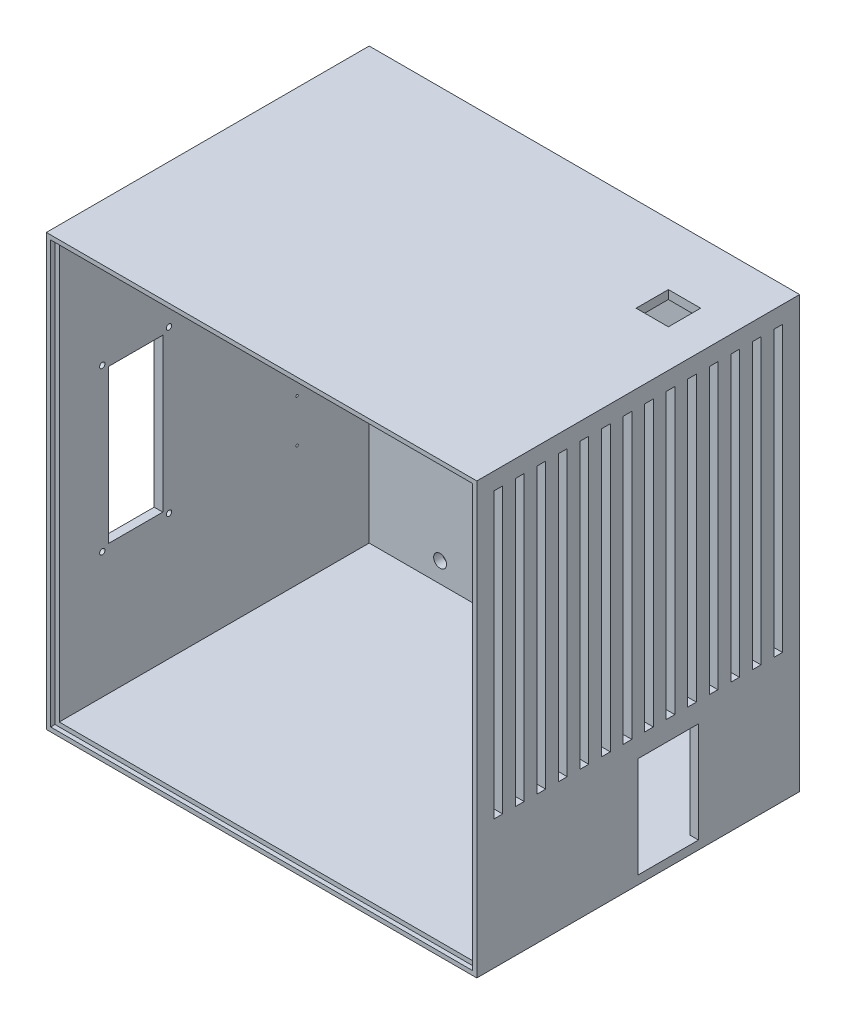
SolidWorks part; units mm, degrees
ref_plane "Front Plane" through (0, 0, 0) normal (0, 0, 1) x (1, 0, 0)
ref_plane "Top Plane" through (0, 0, 0) normal (0, 1, 0) x (1, 0, 0)
ref_plane "Right Plane" through (0, 0, 0) normal (1, 0, 0) x (0, 0, -1)
sketch "Sketch4" plane through (0, 0, 0) normal (0, 0, 1) x (1, 0, 0)
  line L1 (0, 0) -> (200, 0)
  line L2 (0, 0) -> (0, 200)
  line L3 (0, 200) -> (200, 200)
  line L4 (200, 0) -> (200, 200)
  dimension "D1" = 200
  dimension "D2" = 200
extrude "Boss-Extrude1" add sketch "Sketch4" along normal blind 150 contours L2 L1 L4 L3
sketch "Sketch5" plane through (0, 0, 150) normal (0, 0, 1) x (1, 0, 0)
  line L0 (100, 0) -> (100, 2) construction
  line L1 (0, 0) -> (200, 0) construction
  line L2 (0, 100) -> (2, 100) construction
  line L6 (200, 100) -> (198, 100) construction
  line L7 (200, 0) -> (200, 200) construction
  line L8 (100, 200) -> (100, 198) construction
  line L9 (0, 200) -> (200, 200) construction
  line L10 (100, 198) -> (198, 198) construction
  line L11 (198, 198) -> (198, 100) construction
  line L12 (0, 0) -> (0, 200) construction
  line L13 (2, 100) -> (198, 100)
  point P11 (0, 100)
  point P14 (0, 100)
  dimension "D1" = 2
  dimension "D2" = 2
  dimension "D3" = 2
sketch "Sketch6" plane through (0, 0, 150) normal (0, 0, 1) x (1, 0, 0)
  line L0 (2, 100) -> (198, 100) construction
  line L1 (2, 2) -> (198, 2)
  line L2 (2, 2) -> (2, 198)
  line L3 (2, 198) -> (198, 198)
  line L4 (198, 2) -> (198, 198)
  line L5 (2, 2) -> (198, 198) construction
  line L6 (2, 198) -> (198, 2) construction
  point P0 (100, 100)
extrude "Cut-Extrude1" cut sketch "Sketch6" against normal blind 2 contours L2 L1 L4 L3
sketch "Sketch7" plane through (0, 0, 148) normal (0, 0, 1) x (1, 0, 0)
  line L0 (100, 198) -> (100, 196) construction
  line L1 (2, 100) -> (4, 100) construction
  line L2 (2, 100) -> (198, 100) construction
  line L3 (198, 100) -> (196, 100) construction
  line L4 (100, 2) -> (100, 4) construction
  line L6 (4, 4) -> (196, 4)
  line L7 (4, 4) -> (4, 196)
  line L8 (4, 196) -> (196, 196)
  line L9 (196, 4) -> (196, 196)
  line L10 (4, 4) -> (196, 196) construction
  line L11 (4, 196) -> (196, 4) construction
  point P14 (100, 100)
  dimension "D1" = 2
  dimension "D2" = 2
  dimension "D3" = 2
extrude "Cut-Extrude2" cut sketch "Sketch7" against normal blind 92
sketch "Sketch9" plane through (200, 0, 0) normal (1, 0, 0) x (0, 0, -1)
  line L0 (-150, 100) -> (0, 100) construction
  line L1 (-150, 0) -> (-150, 200) construction
  line L2 (0, 0) -> (0, 200) construction
  line L3 (-75, 200) -> (-75, 0) construction
  line L4 (-150, 0) -> (0, 0) construction
  line L5 (0, 0) -> (0, 4) construction
  line L6 (0, 0) -> (-4, 0) construction
  line L7 (-4, 0) -> (-4, 4) construction
  line L8 (-4, 4) -> (0, 4) construction
  line L9 (-4, 4) -> (-150, 4) construction
  line L10 (-75, 0) -> (-75, 4) construction
  line L11 (-150, 200) -> (0, 200) construction
  line L12 (-75, 4) -> (-47, 4)
  line L13 (-75, 4) -> (-75, 50.8)
  line L14 (-75, 50.8) -> (-47, 50.8)
  line L15 (-47, 4) -> (-47, 50.8)
  dimension "D1" = 4
  dimension "D2" = 4
  dimension "D3" = 28
  dimension "D4" = 46.8
sketch "Sketch11" plane through (0, 0, 0) normal (-1, 0, 0) x (0, 0, 1)
  line L0 (75, 0) -> (75, 200) construction
  line L2 (150, 0) -> (0, 0) construction
  line L3 (150, 200) -> (0, 200) construction
  line L5 (150, 0) -> (150, 200) construction
  line L6 (75, 0) -> (75, 4) construction
  line L7 (150, 100) -> (146, 100) construction
  line L10 (75, 4) -> (150, 4) construction
  line L11 (146, 100) -> (146, 4) construction
  line L12 (75, 100) -> (150, 100) construction
  line L13 (99.9, 64.4) -> (125.1, 64.4)
  line L14 (99.9, 64.4) -> (99.9, 135.6)
  line L15 (99.9, 135.6) -> (125.1, 135.6)
  line L16 (125.1, 64.4) -> (125.1, 135.6)
  line L17 (99.9, 64.4) -> (125.1, 135.6) construction
  line L18 (99.9, 135.6) -> (125.1, 64.4) construction
  line L19 (94.5, 60) -> (130.5, 60)
  line L20 (94.5, 60) -> (94.5, 140)
  line L21 (94.5, 140) -> (130.5, 140)
  line L22 (130.5, 60) -> (130.5, 140)
  line L23 (94.5, 60) -> (130.5, 140) construction
  line L24 (94.5, 140) -> (130.5, 60) construction
  line L25 (97, 62.5) -> (128, 62.5)
  line L26 (97, 62.5) -> (97, 137.5)
  line L27 (97, 137.5) -> (128, 137.5)
  line L28 (128, 62.5) -> (128, 137.5)
  line L29 (97, 62.5) -> (128, 137.5) construction
  line L30 (97, 137.5) -> (128, 62.5) construction
  circle A0 centre (128, 137.5) radius 1.25
  circle A1 centre (97, 137.5) radius 1.25
  circle A2 centre (97, 62.5) radius 1.25
  circle A3 centre (128, 62.5) radius 1.25
  point P8 (112.5, 100)
  point P19 (112.5, 100)
  point P24 (112.5, 100)
  dimension "D1" = 4
  dimension "D2" = 4
  dimension "D9" = 2.5
  dimension "D10" = 2.5
  dimension "D11" = 2.5
  dimension "D12" = 2.5
  dimension "D3" = 25.2
  dimension "D4" = 71.2
  dimension "D5" = 36
  dimension "D6" = 80
  dimension "D7" = 75
  dimension "D8" = 31
sketch "Sketch12" plane through (0, 0, 0) normal (-1, 0, 0) x (0, 0, 1)
  line L0 (75, 200) -> (75, 0) construction
  line L1 (150, 200) -> (0, 200) construction
  line L2 (150, 0) -> (0, 0) construction
  line L3 (75, 100) -> (0, 100) construction
  line L4 (150, 0) -> (150, 200) construction
  line L5 (0, 0) -> (0, 200) construction
  line L6 (0, 200) -> (4, 200) construction
  line L7 (0, 200) -> (0, 196) construction
  line L8 (4, 200) -> (4, 0) construction
  line L9 (0, 196) -> (150, 196) construction
  line L10 (37.5, 100) -> (37.5, 196) construction
  line L11 (37.5, 100) -> (37.5, 0) construction
  circle A0 centre (37.5, 100) radius 0.55
  circle A1 centre (37.5, 80) radius 0.55
  circle A2 centre (37.5, 60) radius 0.55
  circle A3 centre (37.5, 148) radius 1
  dimension "D1" = 4
  dimension "D2" = 4
  dimension "D3" = 1.1
  dimension "D5" = 2
sketch "Sketch13" plane through (200, 0, 0) normal (1, 0, 0) x (0, 0, -1)
  line L0 (-4, 4) -> (-4, 200) construction
  line L1 (-150, 200) -> (0, 200) construction
  line L2 (-75, 200) -> (-75, 196) construction
  line L3 (-75, 200) -> (-75, 0) construction
  line L4 (-150, 100) -> (-146, 100) construction
  line L5 (-150, 100) -> (0, 100) construction
  line L6 (-4, 196) -> (-146, 196) construction
  line L7 (-146, 196) -> (-146, 4) construction
  line L8 (-4, 4) -> (-150, 4) construction
  line L9 (-4, 196) -> (-4, 192) construction
  line L10 (-4, 196) -> (-8, 196) construction
  line L11 (-8, 196) -> (-8, 192) construction
  line L12 (-8, 192) -> (-4, 192) construction
  line L13 (-75, 100) -> (-75, 60) construction
  line L14 (-75, 60) -> (-4, 60) construction
  line L15 (-146, 196) -> (-142, 196) construction
  line L16 (-8, 192) -> (-12, 192)
  line L17 (-8, 192) -> (-8, 60)
  line L18 (-8, 60) -> (-12, 60)
  line L19 (-12, 192) -> (-12, 60)
  line L20 (-146, 196) -> (-146, 192) construction
  line L21 (-142, 196) -> (-142, 192) construction
  line L22 (-142, 192) -> (-146, 192) construction
  line L23 (-18, 192) -> (-18, 60)
  line L24 (-18, 192) -> (-22, 192)
  line L25 (-22, 192) -> (-22, 60)
  line L26 (-18, 60) -> (-22, 60)
  line L27 (-28, 192) -> (-28, 60)
  line L28 (-28, 192) -> (-32, 192)
  line L29 (-32, 192) -> (-32, 60)
  line L30 (-28, 60) -> (-32, 60)
  line L31 (-38, 192) -> (-38, 60)
  line L32 (-38, 192) -> (-42, 192)
  line L33 (-42, 192) -> (-42, 60)
  line L34 (-38, 60) -> (-42, 60)
  line L35 (-48, 192) -> (-48, 60)
  line L36 (-48, 192) -> (-52, 192)
  line L37 (-52, 192) -> (-52, 60)
  line L38 (-48, 60) -> (-52, 60)
  line L39 (-58, 192) -> (-58, 60)
  line L40 (-58, 192) -> (-62, 192)
  line L41 (-62, 192) -> (-62, 60)
  line L42 (-58, 60) -> (-62, 60)
  line L43 (-68, 192) -> (-68, 60)
  line L44 (-68, 192) -> (-72, 192)
  line L45 (-72, 192) -> (-72, 60)
  line L46 (-68, 60) -> (-72, 60)
  line L47 (-78, 192) -> (-78, 60)
  line L48 (-78, 192) -> (-82, 192)
  line L49 (-82, 192) -> (-82, 60)
  line L50 (-78, 60) -> (-82, 60)
  line L51 (-88, 192) -> (-88, 60)
  line L52 (-88, 192) -> (-92, 192)
  line L53 (-92, 192) -> (-92, 60)
  line L54 (-88, 60) -> (-92, 60)
  line L55 (-98, 192) -> (-98, 60)
  line L56 (-98, 192) -> (-102, 192)
  line L57 (-102, 192) -> (-102, 60)
  line L58 (-98, 60) -> (-102, 60)
  line L59 (-108, 192) -> (-108, 60)
  line L60 (-108, 192) -> (-112, 192)
  line L61 (-112, 192) -> (-112, 60)
  line L62 (-108, 60) -> (-112, 60)
  line L63 (-118, 192) -> (-118, 60)
  line L64 (-118, 192) -> (-122, 192)
  line L65 (-122, 192) -> (-122, 60)
  line L66 (-118, 60) -> (-122, 60)
  line L67 (-128, 192) -> (-128, 60)
  line L68 (-128, 192) -> (-132, 192)
  line L69 (-132, 192) -> (-132, 60)
  line L70 (-128, 60) -> (-132, 60)
  line L71 (-138, 192) -> (-138, 60)
  line L72 (-138, 192) -> (-142, 192)
  line L73 (-142, 192) -> (-142, 60)
  line L74 (-138, 60) -> (-142, 60)
  dimension "D1" = 4
  dimension "D2" = 4
  dimension "D3" = 4
  dimension "D4" = 4
  dimension "D5" = 40
  dimension "D6" = 4
  dimension "D7" = 4
  dimension "D8" = 14
extrude "Inlet" cut sketch "Sketch9" against normal blind 4 contours L13 L12 L15 L14
extrude "Airflow" cut sketch "Sketch13" against normal blind 4
extrude "Cut-Extrude5" cut sketch "Sketch11" against normal blind 4 contours L14 L13 L16 L15
extrude "LCD/Mounting" cut sketch "Sketch11<4>" against normal blind 4 contours A2 | A0 | A1 | A3
sketch "Sketch11<4>" plane through (0, 0, 0) normal (-1, 0, 0) x (0, 0, 1) same geometry as "Sketch11"
extrude "Post/Knob Mounting" cut sketch "Sketch12" against normal blind 4
sketch "Sketch14" plane through (0, 0, 56) normal (0, 0, 1) x (1, 0, 0)
  line L0 (100, 4) -> (100, 109) construction
  line L1 (176, 9) -> (171.555, 9) construction
  line L2 (4, 4) -> (196, 4) construction
  line L3 (4, 4) -> (4, 9) construction
  line L4 (4, 196) -> (4, 4) construction
  line L5 (4, 9) -> (196, 9) construction
  line L6 (196, 4) -> (196, 50.8) construction
  line L7 (171.555, 9) -> (171.555, 13.318) construction
  line L8 (176, 108.06) -> (171.555, 108.06) construction
  line L9 (196, 4) -> (176, 4) construction
  line L10 (4, 4) -> (196, 4) construction
  line L11 (176, 4) -> (176, 9) construction
  line L12 (171.555, 108.06) -> (171.555, 104.25) construction
  line L13 (176, 9) -> (33.125, 9)
  line L14 (176, 9) -> (176, 108.06)
  line L15 (176, 108.06) -> (33.125, 108.06)
  line L16 (33.125, 9) -> (33.125, 108.06)
  line L17 (33.125, 9) -> (36.935, 9) construction
  line L18 (36.935, 9) -> (36.935, 13.318) construction
  line L19 (33.125, 108.06) -> (37.506, 108.06) construction
  line L20 (37.506, 108.06) -> (37.506, 103.996) construction
  line L22 (4, 196) -> (196, 196)
  line L23 (4, 196) -> (4, 4)
  line L24 (4, 4) -> (196, 4)
  line L25 (196, 196) -> (196, 4)
  circle A0 centre (36.935, 13.318) radius 3
  circle A1 centre (171.555, 13.318) radius 3
  circle A2 centre (171.555, 104.25) radius 3
  circle A3 centre (37.506, 103.996) radius 3
  dimension "D14" = 6
  dimension "D15" = 6
  dimension "D16" = 6
  dimension "D17" = 6
  dimension "D1" = 105
  dimension "D2" = 5
  dimension "D3" = 20
  dimension "D4" = 142.875
  dimension "D5" = 99.06
  dimension "D6" = 4.445
  dimension "D7" = 4.318
  dimension "D8" = 4.445
  dimension "D9" = 3.81
  dimension "D10" = 3.81
  dimension "D11" = 4.318
  dimension "D12" = 4.381
  dimension "D13" = 4.064
extrude "Cut-Extrude10" cut sketch "Sketch14" against normal blind 56 contours A3 | A2 | A0 | A1 region at (36.935, 13.318, 56) region at (171.555, 104.25, 56) region at (37.506, 103.996, 56)
sketch "Sketch17" plane through (0, 0, 56) normal (0, 0, 1) x (1, 0, 0)
  line L1 (4, 4) -> (196, 4)
  line L2 (4, 4) -> (4, 196)
  line L3 (4, 196) -> (196, 196)
  line L4 (196, 4) -> (196, 196)
extrude "Cut-Extrude11" cut sketch "Sketch17" against normal blind 52
sketch "Sketch18" plane through (0, 0, 4) normal (0, 0, 1) x (1, 0, 0)
  line L0 (100, 196) -> (100, 4) construction
  line L1 (196, 196) -> (4, 196) construction
  line L2 (4, 4) -> (196, 4) construction
  line L3 (4, 196) -> (4, 191) construction
  line L4 (4, 196) -> (4, 4) construction
  line L5 (4, 191) -> (196, 191) construction
  line L6 (196, 4) -> (196, 196) construction
  line L7 (4, 196) -> (52, 196) construction
  line L8 (196, 196) -> (4, 196) construction
  line L9 (196, 196) -> (148, 196) construction
  line L10 (52, 196) -> (76, 196) construction
  line L11 (76, 196) -> (76, 4) construction
  line L12 (76, 196) -> (76, 191) construction
  line L13 (142.04, 191) -> (126.8, 191) construction
  line L14 (76, 191) -> (142.04, 191)
  line L15 (76, 191) -> (76, 140.2)
  line L16 (76, 140.2) -> (142.04, 140.2)
  line L17 (142.04, 191) -> (142.04, 140.2)
  line L18 (126.8, 191) -> (126.8, 188.46) construction
  line L19 (126.8, 188.46) -> (126.8, 140.2) construction
  line L20 (126.8, 140.2) -> (126.8, 142.74) construction
  line L21 (76, 140.2) -> (76, 157.98) construction
  line L22 (76, 140.2) -> (76, 185.92)
  circle A0 centre (126.8, 188.46) radius 1.6
  circle A1 centre (126.8, 142.74) radius 1.6
  circle A2 centre (76, 157.98) radius 1.6
  circle A3 centre (76, 185.92) radius 1.6
  dimension "D12" = 3.2
  dimension "D13" = 3.2
  dimension "D14" = 3.2
  dimension "D15" = 3.2
  dimension "D1" = 5
  dimension "D2" = 48
  dimension "D3" = 48
  dimension "D4" = 24
  dimension "D5" = 66.04
  dimension "D6" = 50.8
  dimension "D7" = 15.24
  dimension "D8" = 2.54
  dimension "D9" = 2.54
  dimension "D10" = 17.78
  dimension "D11" = 45.72
extrude "Cut-Extrude12" cut sketch "Sketch18" against normal blind 4 contours A3 | A0 | A2 | A1
sketch "Sketch20" plane through (0, 200, 0) normal (0, 1, 0) x (1, 0, 0)
  line L0 (100, 0) -> (100, -150) construction
  line L1 (0, 0) -> (200, 0) construction
  line L2 (0, -150) -> (200, -150) construction
  line L3 (200, -72) -> (0, -72) construction
  line L4 (0, -150) -> (0, 0) construction
  line L5 (200, 0) -> (200, -36) construction
  line L6 (200, -150) -> (200, 0) construction
  line L7 (200, -36) -> (100, -36) construction
  line L8 (150, -36) -> (150, 0) construction
  line L9 (150, -18) -> (200, -18) construction
  line L10 (175, -18) -> (175, -36) construction
  line L12 (167.5, -28.5) -> (182.5, -28.5)
  line L13 (167.5, -28.5) -> (167.5, -43.5)
  line L14 (167.5, -43.5) -> (182.5, -43.5)
  line L15 (182.5, -28.5) -> (182.5, -43.5)
  line L16 (167.5, -28.5) -> (182.5, -43.5) construction
  line L17 (167.5, -43.5) -> (182.5, -28.5) construction
  dimension "D1" = 36
  dimension "D2" = 15
  dimension "D3" = 15
extrude "Cut-Extrude13" cut sketch "Sketch20" against normal blind 4 contours L13 L12 L15 L14
equation "\"L\"= 100mm"
equation "\"T\"= 1mm"
equation "\"D1@Sketch4\"=2*\"L\""
equation "\"D2@Sketch4\"=2*\"L\""
equation "\"D1@Boss-Extrude1\"=1.5*\"L\""
equation "\"D1@Sketch5\"=(1/50)*\"L\""
equation "\"D2@Sketch5\"=(1/50)*\"L\""
equation "\"D3@Sketch5\"=(1/50)*\"L\""
equation "\"D4@Sketch5\"=(1/50)*\"L\""
equation "\"D1@Cut-Extrude1\"=(1/50)*\"L\""
equation "\"D1@Sketch7\"=(1/50)*\"L\""
equation "\"D2@Sketch7\"=(1/50)*\"L\""
equation "\"D3@Sketch7\"=(1/50)*\"L\""
equation "\"D4@Sketch7\"=(1/50)*\"L\""
equation "\"D1@Sketch9\"=4*\"T\""
equation "\"D2@Sketch9\"=4*\"T\""
equation "\"D3@Sketch9\"=(7/25)*\"L\""
equation "\"D4@Sketch9\"=(46.8/100)*\"L\""
equation "\"D1@Sketch11\"=4*\"T\""
equation "\"D2@Sketch11\"=4*\"T\""
equation "\"D3@Sketch11\"=(25.2/100)*\"L\""
equation "\"D4@Sketch11\"=(71.2/100)*\"L\""
equation "\"D5@Sketch11\"=(9/25)*\"L\""
equation "\"D6@Sketch11\"=(4/5)*\"L\""
equation "\"D7@Sketch11\"=(3/4)*\"L\""
equation "\"D8@Sketch11\"=(31/100)*\"L\""
equation "\"D9@Sketch11\"=(1/40)*\"L\""
equation "\"D10@Sketch11\"=(1/40)*\"L\""
equation "\"D11@Sketch11\"=(1/40)*\"L\""
equation "\"D12@Sketch11\"=(1/40)*\"L\""
equation "\"D1@Sketch12\"=4*\"T\""
equation "\"D2@Sketch12\"=4*\"T\""
equation "\"D3@Sketch12\"=(1.1/100)*\"L\""
equation "\"D5@Sketch12\"=(1/50)*\"L\""
equation "\"D1@Sketch13\"=4*\"T\""
equation "\"D2@Sketch13\"=4*\"T\""
equation "\"D3@Sketch13\"=4*\"T\""
equation "\"D4@Sketch13\"=4*\"T\""
equation "\"D5@Sketch13\"=(2/5)*\"L\""
equation "\"D6@Sketch13\"=4*\"T\""
equation "\"D7@Sketch13\"=4*\"T\""
